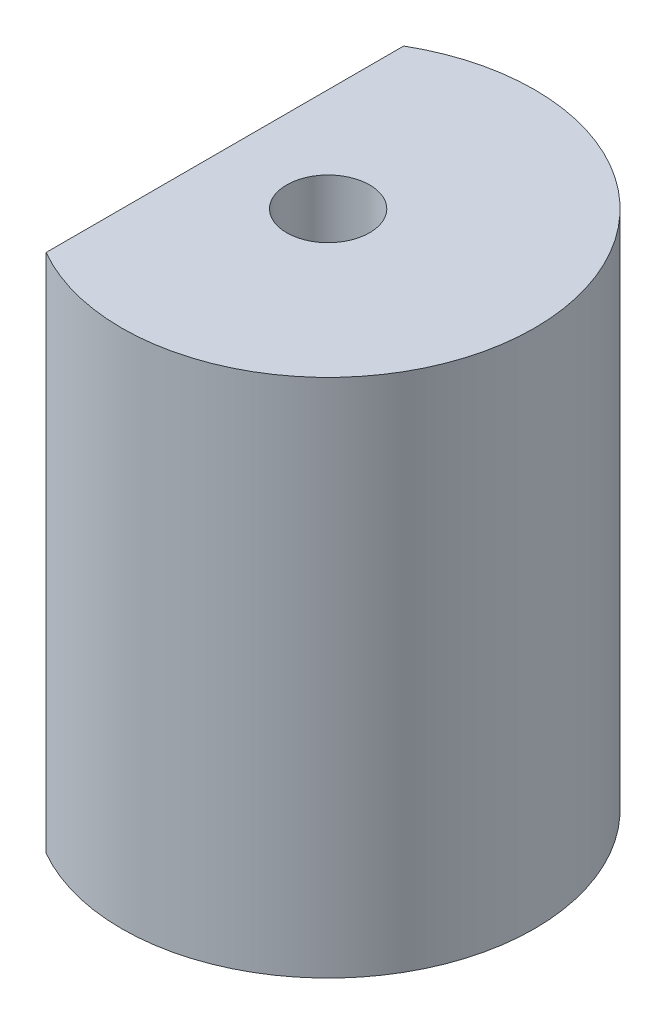
SolidWorks part; units mm, degrees
material "Delrin 2700 NC010, Low Viscosity Acetal Copolymer (SS)"
ref_plane "Front Plane" through (0, 0, 0) normal (0, 0, 1) x (1, 0, 0)
ref_plane "Top Plane" through (0, 0, 0) normal (0, 1, 0) x (1, 0, 0)
ref_plane "Right Plane" through (0, 0, 0) normal (1, 0, 0) x (0, 0, -1)
sketch "Sketch1" plane through (0, 0, 0) normal (0, 1, 0) x (1, 0, 0)
  circle A0 centre (0, 0) radius 12.7
  dimension "D1" = 25.4
extrude "Boss-Extrude1" add sketch "Sketch1" along normal blind 32
sketch "Sketch2" plane through (0, 0, 0) normal (0, -1, 0) x (1, 0, 0)
  point P0 (0, 0)
hole_wizard "Tap Drill for 1/4-20 Tap1" positions "Sketch2" profile "Sketch3" hole size "1/4-20" standard "ANSI Inch"
sketch "Sketch3" plane through (0, 0, 0) normal (1, 0, 0) x (0, 0, -1)
  line L0 (0, 0) -> (0, 11.6938)
  line L1 (0, 11.6938) -> (2.5527, 10.16)
  line L2 (2.5527, 10.16) -> (2.5527, 0)
  line L5 (2.5527, 0) -> (0, 0)
  line L10 (0, 11.6938) -> (-2.5527, 10.16) construction
  line L11 (0, -6.35) -> (0, 107.95) construction
  dimension "Hole Dia." = 5.1054
  dimension "Hole Depth" = 10.16
  dimension "Drill Angle" = 118
sketch "Sketch4" plane through (0, 32, 0) normal (0, 1, 0) x (1, 0, 0)
  point P0 (0, 0)
hole_wizard "Tap Drill for 1/4-20 Tap2" positions "Sketch4" profile "Sketch5" hole size "1/4-20" standard "ANSI Inch"
sketch "Sketch5" plane through (0, 32, 0) normal (1, 0, 0) x (0, 0, 1)
  line L0 (0, 0) -> (0, 11.6938)
  line L1 (0, 11.6938) -> (2.5527, 10.16)
  line L2 (2.5527, 10.16) -> (2.5527, 0)
  line L5 (2.5527, 0) -> (0, 0)
  line L10 (0, 11.6938) -> (-2.5527, 10.16) construction
  line L11 (0, -6.35) -> (0, 107.95) construction
  dimension "Hole Dia." = 5.1054
  dimension "Hole Depth" = 10.16
  dimension "Drill Angle" = 118
sketch "Sketch6" plane through (0, 32, 0) normal (0, 1, 0) x (1, 0, 0)
  line L0 (-6.35, 10.9985) -> (-6.35, -10.9985)
  circle A0 centre (0, 0) radius 12.7 construction
  arc A1 (-6.35, 10.9985) -> (-6.35, -10.9985) centre (0, 0) ccw
  point P5 (-12.7, 0)
  dimension "D1" = 6.35
extrude "Cut-Extrude1" cut sketch "Sketch6" against normal through all
